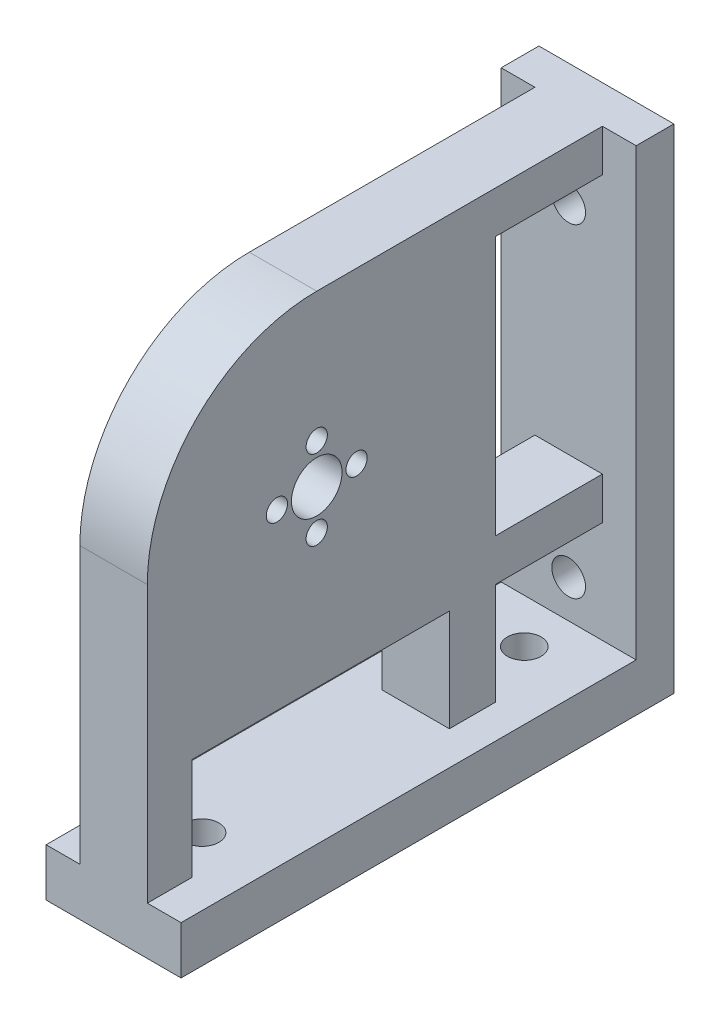
SolidWorks part; units mm, degrees
ref_plane "Front Plane" through (0, 0, 0) normal (0, 0, 1) x (1, 0, 0)
ref_plane "Top Plane" through (0, 0, 0) normal (0, 1, 0) x (1, 0, 0)
ref_plane "Right Plane" through (0, 0, 0) normal (1, 0, 0) x (0, 0, -1)
sketch "Sketch1" plane through (0, 0, 0) normal (1, 0, 0) x (0, 0, -1)
  line L11 (0, 31.8822) -> (31.8822, 31.8822)
  line L12 (31.8822, 31.8822) -> (60.8746, 31.8822)
  line L16 (60.8746, 31.8822) -> (60.8746, -60.96)
  line L17 (-31.8822, 0) -> (-31.8822, -60.96)
  line L18 (60.8746, -60.96) -> (-31.8822, -60.96)
  circle A1 centre (0, 0) radius 4.7625
  arc A3 (0, 31.8822) -> (-31.8822, 0) centre (0, 0) ccw
extrude "Boss-Extrude1" add sketch "Sketch1" along normal blind 12.7
sketch "Sketch8" plane through (12.7, 0, 0) normal (1, 0, 0) x (0, 0, -1)
  line L0 (-31.8822, -60.96) -> (60.8746, -60.96) construction
  line L1 (60.8746, 31.8822) -> (53.7706, 31.8822)
  line L2 (60.8746, 31.8822) -> (60.8746, -60.96)
  line L3 (60.8746, -60.96) -> (53.7706, -60.96)
  line L4 (53.7706, 31.8822) -> (53.7706, -51.9379)
  line L5 (-31.8822, 0) -> (-31.8822, -60.96) construction
  line L6 (53.7706, -60.96) -> (-31.8822, -60.96)
  line L8 (53.7706, -51.9379) -> (-31.8822, -51.9379)
  line L9 (-31.8822, -60.96) -> (-31.8822, -51.9379)
extrude "Boss-Extrude2" add sketch "Sketch8" along normal blind 6.35 and the other way blind 19.05
fillet "Fillet1" [suppressed] radius 2.54
mirror "Mirror1" [suppressed] about plane through (0, 0, 0) normal (0, 0, 1)
fillet "Fillet2" [suppressed] radius 5.08
sketch "Sketch4" plane through (0, 0, 0) normal (-1, 0, 0) x (0, 0, 1)
  line L4 (-53.7706, 23.9633) -> (-33.6922, 23.9633)
  line L5 (-33.6922, 23.9633) -> (-33.6922, -24.8177)
  line L6 (-24.9665, -32.7419) -> (23.4543, -32.7419)
  line L7 (23.4543, -32.7419) -> (23.4543, -51.9379)
  line L8 (23.4543, -51.9379) -> (-24.9665, -51.9379)
  line L9 (-53.7706, -51.9379) -> (-53.7706, -32.7419)
  line L10 (-33.6922, -32.7419) -> (-33.6922, -51.9379)
  line L11 (-24.9665, -51.9379) -> (-24.9665, -32.7419)
  line L12 (-33.6922, -51.9379) -> (-53.7706, -51.9379)
  line L13 (-33.6922, -32.7419) -> (-53.7706, -32.7419)
  line L14 (-33.6922, -24.8177) -> (-53.7706, -24.8177)
  line L15 (-53.7706, -24.8177) -> (-53.7706, 23.9633)
extrude "Cut-Extrude2" cut sketch "Sketch4" against normal blind 26.162
sketch "Sketch5" plane through (0, 0, -60.8746) normal (0, 0, -1) x (-1, 0, 0)
  circle A0 centre (-6.35, 16.187) radius 3.175
  circle A1 centre (-6.35, -44.7886) radius 3.175
extrude "Cut-Extrude3" cut sketch "Sketch5" against normal blind 11.43
sketch "Sketch6" plane through (0, -60.96, 0) normal (0, -1, 0) x (1, 0, 0)
  circle A0 centre (6.35, 15.24) radius 3.175
  circle A1 centre (6.35, -45.4106) radius 3.175
extrude "Cut-Extrude4" cut sketch "Sketch6" against normal blind 11.43
sketch "Sketch9" plane through (0, 0, 0) normal (-1, 0, 0) x (0, 0, 1)
  line L1 (-33.6922, -24.8177) -> (-71.3105, -24.8177)
  line L2 (-33.6922, -24.8177) -> (-33.6922, 42.9585)
  line L3 (-33.6922, 42.9585) -> (-71.3105, 42.9585)
  line L4 (-71.3105, -24.8177) -> (-71.3105, 42.9585)
extrude "Cut-Extrude5" [suppressed] cut sketch "Sketch9" against normal blind 41.656 and the other way blind 46.736
fillet "Fillet3" [suppressed] radius 33.02
sketch "Sketch11" plane through (12.7, 0, 0) normal (1, 0, 0) x (0, 0, -1)
  circle A1 centre (7.5, 0) radius 2
  circle A2 centre (0, -7.5) radius 2
  circle A3 centre (-7.5, 0) radius 2
  circle A4 centre (0, 7.5) radius 2
  point P14 (0, 0)
  dimension "D1" = 4
extrude "Cut-Extrude7" cut sketch "Sketch11" against normal blind 21.844
